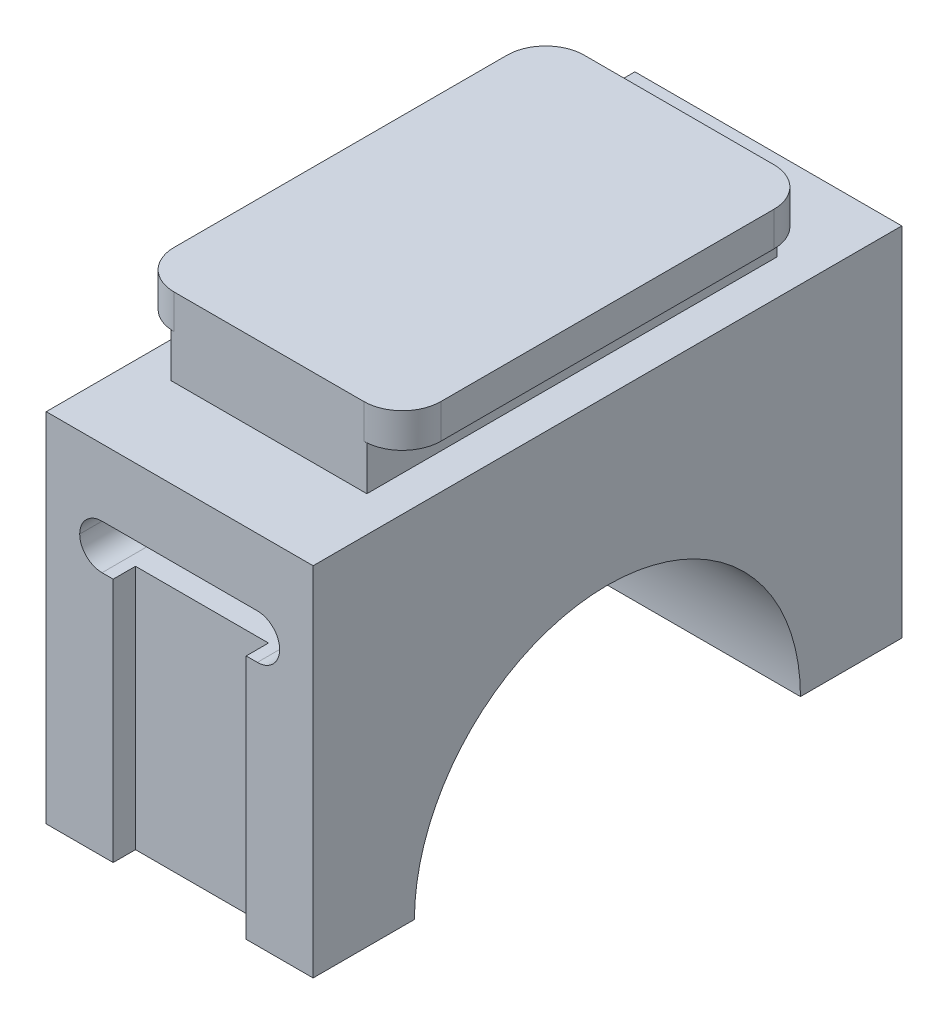
SolidWorks part; units mm, degrees
material "ABS"
ref_plane "Front Plane" through (0, 0, 0) normal (0, 0, 1) x (1, 0, 0)
ref_plane "Top Plane" through (0, 0, 0) normal (0, 1, 0) x (1, 0, 0)
ref_plane "Right Plane" through (0, 0, 0) normal (1, 0, 0) x (0, 0, -1)
sketch "Sketch1" plane through (0, 0, 0) normal (0, 1, 0) x (1, 0, 0)
  line L1 (2.1971, 0) -> (12.9921, 0)
  line L2 (0, -2.1971) -> (0, -21.1455)
  line L3 (2.1971, -23.3426) -> (12.9921, -23.3426)
  line L4 (15.1892, -2.1971) -> (15.1892, -21.1455)
  arc A0 (0, -21.1455) -> (2.1971, -23.3426) centre (2.1971, -21.1455) ccw
  arc A1 (12.9921, -23.3426) -> (15.1892, -21.1455) centre (12.9921, -21.1455) ccw
  arc A2 (12.9921, 0) -> (15.1892, -2.1971) centre (12.9921, -2.1971) cw
  arc A3 (2.1971, 0) -> (0, -2.1971) centre (2.1971, -2.1971) ccw
  point P7 (0, -23.3426)
  point P12 (15.1892, 0)
  point P15 (0, 0)
  dimension "D3" = 2.1971
  dimension "D1" = 15.1892
  dimension "D2" = 23.3426
extrude "Boss-Extrude1" add sketch "Sketch1" along normal blind 1.9558
sketch "Sketch2" plane through (0, 0, 0) normal (0, -1, 0) x (1, 0, 0)
  line L0 (12.9921, 0) -> (2.1971, 0) construction
  line L1 (13.1699, 0) -> (2.0193, 0)
  line L2 (13.1699, 0) -> (13.1699, 23.3426)
  line L3 (13.1699, 23.3426) -> (2.0193, 23.3426)
  line L4 (2.0193, 0) -> (2.0193, 23.3426)
  line L7 (2.1971, 23.3426) -> (12.9921, 23.3426) construction
  line L8 (0, 2.1971) -> (0, 21.1455) construction
  line L9 (15.1892, 21.1455) -> (15.1892, 2.1971) construction
  dimension "D1" = 2.0193
  dimension "D2" = 2.0193
extrude "Boss-Extrude2" add sketch "Sketch2" along normal blind 2.5019
sketch "Sketch3" plane through (0, -2.5019, 0) normal (0, -1, 0) x (1, 0, 0)
  line L0 (15.1892, 21.1455) -> (15.1892, 2.1971) construction
  line L1 (15.1892, -5.08) -> (0, -5.08)
  line L2 (15.1892, -5.08) -> (15.1892, 28.4226)
  line L3 (15.1892, 28.4226) -> (0, 28.4226)
  line L4 (0, -5.08) -> (0, 28.4226)
  line L5 (0, 2.1971) -> (0, 21.1455) construction
  line L6 (13.1699, 23.3426) -> (2.0193, 23.3426) construction
  line L7 (2.0193, 0) -> (13.1699, 0) construction
  dimension "D1" = 5.08
  dimension "D2" = 5.08
extrude "Boss-Extrude3" add sketch "Sketch3" along normal blind 20.32
sketch "Sketch4" plane through (15.1892, 0, 0) normal (1, 0, 0) x (0, 0, -1)
  line L0 (5.08, -22.8219) -> (-28.4226, -22.8219) construction
  circle A0 centre (-11.6713, -22.8219) radius 10.9855
  dimension "D1" = 21.971
extrude "Cut-Extrude1" cut sketch "Sketch4" against normal through all
sketch "Sketch5" plane through (0, 0, 28.4226) normal (0, 0, 1) x (1, 0, 0)
  line L0 (15.1892, -2.5019) -> (0, -2.5019) construction
  line L1 (1.905, -6.3119) -> (13.2842, -6.3119)
  line L2 (1.905, -6.3119) -> (1.905, -8.8519)
  line L3 (1.905, -8.8519) -> (13.2842, -8.8519)
  line L4 (13.2842, -6.3119) -> (13.2842, -8.8519)
  line L5 (15.1892, -22.8219) -> (15.1892, -2.5019) construction
  line L6 (0, -22.8219) -> (0, -2.5019) construction
  dimension "D1" = 3.81
  dimension "D2" = 1.905
  dimension "D3" = 1.905
  dimension "D4" = 2.54
extrude "Cut-Extrude2" cut sketch "Sketch5" against normal through all
fillet "Fillet1" radius 1.27 4 edges at (13.2842, -8.8519, 11.6713) (13.2842, -6.3119, 11.6713) (1.905, -6.3119, 11.6713) (1.905, -8.8519, 11.6713)
sketch "Sketch6" plane through (0, 0, -5.08) normal (0, 0, -1) x (-1, 0, 0)
  line L0 (-3.175, -8.8519) -> (-12.0142, -8.8519) construction
  line L1 (-11.3792, -8.8519) -> (-3.81, -8.8519)
  line L2 (-11.3792, -8.8519) -> (-11.3792, -22.8219)
  line L3 (-11.3792, -22.8219) -> (-3.81, -22.8219)
  line L4 (-3.81, -8.8519) -> (-3.81, -22.8219)
  line L5 (0, -22.8219) -> (-15.1892, -22.8219) construction
  line L6 (0, -22.8219) -> (0, -2.5019) construction
  line L7 (-15.1892, -22.8219) -> (-15.1892, -2.5019) construction
  dimension "D1" = 3.81
  dimension "D2" = 3.81
extrude "Cut-Extrude3" cut sketch "Sketch6" against normal blind 1.27
sketch "Sketch7" plane through (0, 0, 28.4226) normal (0, 0, 1) x (1, 0, 0)
  line L0 (15.1892, -22.8219) -> (0, -22.8219) construction
  line L1 (11.3792, -22.8219) -> (3.81, -22.8219)
  line L2 (11.3792, -22.8219) -> (11.3792, -8.8519)
  line L3 (11.3792, -8.8519) -> (3.81, -8.8519)
  line L4 (3.81, -22.8219) -> (3.81, -8.8519)
  line L5 (3.175, -8.8519) -> (12.0142, -8.8519) construction
  line L6 (0, -22.8219) -> (0, -2.5019) construction
  line L7 (15.1892, -22.8219) -> (15.1892, -2.5019) construction
  dimension "D1" = 3.81
  dimension "D2" = 3.81
extrude "Cut-Extrude4" cut sketch "Sketch7" against normal blind 1.27
